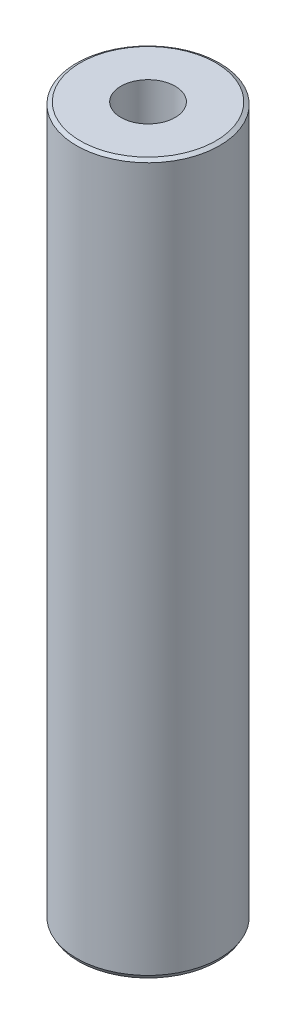
SolidWorks part; units mm, degrees
ref_plane "Front Plane" through (0, 0, 0) normal (0, 0, 1) x (1, 0, 0)
ref_plane "Top Plane" through (0, 0, 0) normal (0, 1, 0) x (1, 0, 0)
ref_plane "Right Plane" through (0, 0, 0) normal (1, 0, 0) x (0, 0, -1)
sketch "Sketch1" plane through (0, 0, 0) normal (0, 1, 0) x (1, 0, 0)
  circle A0 centre (0, 0) radius 37.5
  dimension "SHAFT_OD" = 75
extrude "Boss-Extrude1" add sketch "Sketch1" along normal blind 371.9564
sketch "Sketch2" plane through (0, 0, 0) normal (0, 1, 0) x (1, 0, 0)
  circle A0 centre (0, 0) radius 14.2295
  dimension "BORE_D" = 28.459
extrude "Cut-Extrude1" cut sketch "Sketch2" along normal through all
chamfer "Chamfer1" distance 1.157 angle 60 2 edges at (0, 371.9564, 37.5) (0, 0, 37.5) first distance on face at (0, 371.9564, 37.5) first distance on face at (0, 0, 14.2295)
